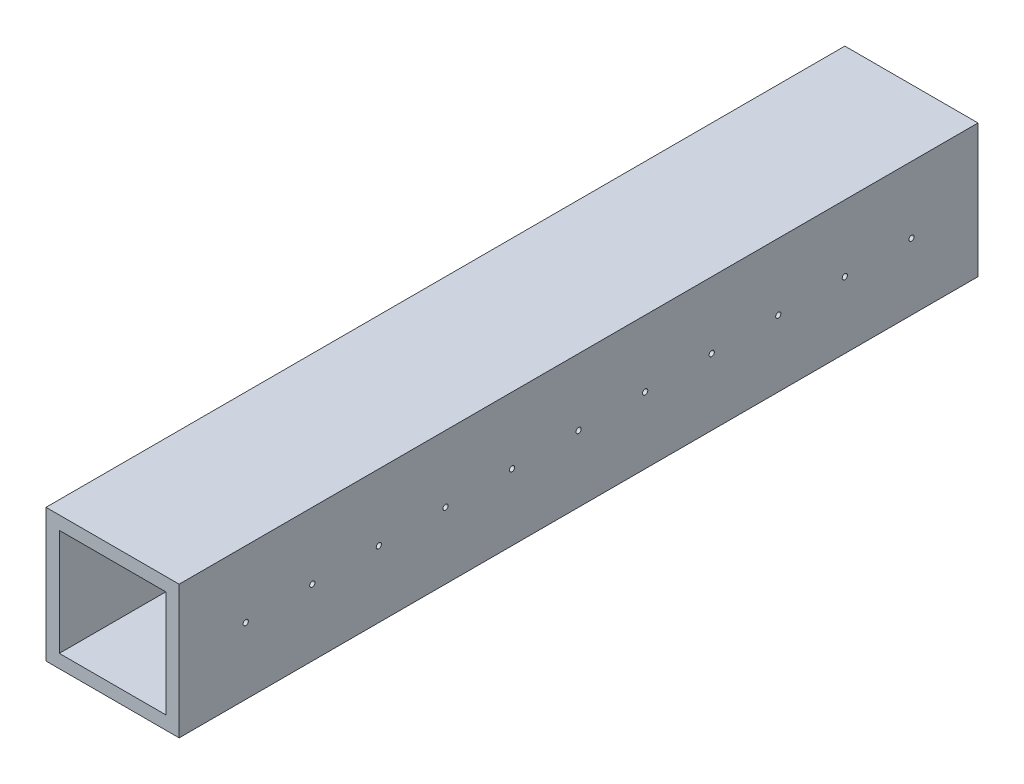
SolidWorks part; units mm, degrees
ref_plane "Front Plane" through (0, 0, 0) normal (0, 0, 1) x (1, 0, 0)
ref_plane "Top Plane" through (0, 0, 0) normal (0, 1, 0) x (1, 0, 0)
ref_plane "Right Plane" through (0, 0, 0) normal (1, 0, 0) x (0, 0, -1)
sketch "Sketch1" plane through (0, 0, 0) normal (0, 0, 1) x (1, 0, 0)
  line L1 (2.0562, 11.0067) -> (22.3762, 11.0067)
  line L2 (2.0562, 11.0067) -> (2.0562, -9.3133)
  line L3 (2.0562, -9.3133) -> (22.3762, -9.3133)
  line L4 (22.3762, 11.0067) -> (22.3762, -9.3133)
  line L5 (-0.4838, 13.5467) -> (24.9162, 13.5467)
  line L6 (-0.4838, 13.5467) -> (-0.4838, -11.8533)
  line L7 (-0.4838, -11.8533) -> (24.9162, -11.8533)
  line L8 (24.9162, 13.5467) -> (24.9162, -11.8533)
  dimension "D1" = 25.4
  dimension "D2" = 25.4
  dimension "D3" = 2.54
  dimension "D4" = 2.54
  dimension "D5" = 2.54
  dimension "D6" = 2.54
extrude "Boss-Extrude1" add sketch "Sketch1" along normal blind 152.4
sketch "Sketch2" plane through (24.9162, 0, 0) normal (1, 0, 0) x (0, 0, -1)
  line L0 (-152.4, 13.5467) -> (0, 13.5467) construction
  line L1 (-152.4, -11.8533) -> (-152.4, 13.5467) construction
  circle A0 centre (-139.7, 0.8467) radius 0.5
  circle A1 centre (-127, 0.8467) radius 0.5
  circle A2 centre (-114.3, 0.8467) radius 0.5
  circle A3 centre (-101.6, 0.8467) radius 0.5
  circle A4 centre (-88.9, 0.8467) radius 0.5
  circle A5 centre (-76.2, 0.8467) radius 0.5
  circle A6 centre (-63.5, 0.8467) radius 0.5
  circle A7 centre (-50.8, 0.8467) radius 0.5
  circle A8 centre (-38.1, 0.8467) radius 0.5
  circle A9 centre (-25.4, 0.8467) radius 0.5
  circle A10 centre (-12.7, 0.8467) radius 0.5
  dimension "D1" = 1
  dimension "D2" = 12.7
  dimension "D3" = 12.7
  dimension "D4" = 11
extrude "Cut-Extrude1" cut sketch "Sketch2" against normal through all both and the other way through all
